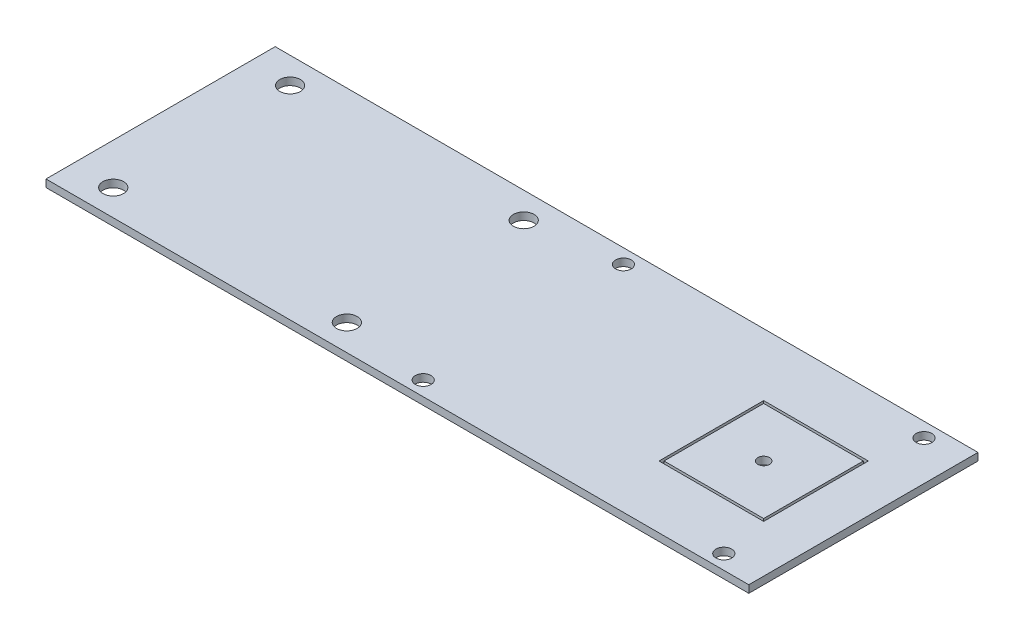
SolidWorks part; units mm, degrees
ref_plane "Front Plane" through (0, 0, 0) normal (0, 0, 1) x (1, 0, 0)
ref_plane "Top Plane" through (0, 0, 0) normal (0, 1, 0) x (1, 0, 0)
ref_plane "Right Plane" through (0, 0, 0) normal (1, 0, 0) x (0, 0, -1)
sketch "Sketch1" plane through (0, 0, 0) normal (0, 1, 0) x (1, 0, 0)
  line L0 (-62.28, 19.825) -> (-62.28, -19.825) construction
  line L1 (-70.525, -23) -> (70.525, -23)
  line L2 (-70.525, -23) -> (-70.525, 23)
  line L3 (-70.525, 23) -> (70.525, 23)
  line L4 (70.525, -23) -> (70.525, 23)
  line L5 (-70.525, -23) -> (70.525, 23) construction
  line L6 (-70.525, 23) -> (70.525, -23) construction
  line L7 (-64.355, -17.75) -> (-13.325, -17.75) construction
  line L8 (2.27, 18.515) -> (2.27, -18.515) construction
  line L9 (3.845, -20.09) -> (61.025, -20.09) construction
  line L10 (-62.28, 17.75) -> (-15.4, -17.75) construction
  circle A0 centre (-62.28, -17.75) radius 2.075
  circle A1 centre (-15.4, -17.75) radius 2.075
  circle A2 centre (-15.4, 17.75) radius 2.075
  circle A3 centre (-62.28, 17.75) radius 2.075
  circle A4 centre (2.27, -20.09) radius 1.575
  circle A5 centre (62.6, -20.09) radius 1.575
  circle A6 centre (62.6, 20.09) radius 1.575
  circle A7 centre (2.27, 20.09) radius 1.575
  circle A8 centre (50.51, 0) radius 1.185
  point P0 (0, 0)
  point P18 (-62.28, 0)
  point P31 (64.175, -20.09)
  point P32 (62.6, -21.665)
  point P33 (51.695, 0)
  point P34 (2.27, 0)
  point P37 (-38.84, 0)
  dimension "D6" = 4.15
  dimension "D12" = 3.15
  dimension "D16" = 2.37
  dimension "D1" = 141.05
  dimension "D2" = 46
  dimension "D5" = 39.65
  dimension "D7" = 6.17
  dimension "D8" = 51.03
  dimension "D11" = 37.03
  dimension "D13" = 57.18
  dimension "D14" = 6.35
  dimension "D15" = 18.83
  dimension "D3" = 2
  dimension "D4" = 2
  dimension "D9" = 2
  dimension "D10" = 2
extrude "Boss-Extrude1" add sketch "Sketch1" along normal blind 1.5
sketch "Sketch2" plane through (0, 1.5, 0) normal (0, 1, 0) x (1, 0, 0)
  line L1 (40.51, -10) -> (60.51, -10)
  line L2 (40.51, -10) -> (40.51, 10)
  line L3 (40.51, 10) -> (60.51, 10)
  line L4 (60.51, -10) -> (60.51, 10)
  line L5 (40.51, -10) -> (60.51, 10) construction
  line L6 (40.51, 10) -> (60.51, -10) construction
  point P0 (50.51, 0)
  dimension "D1" = 20
  dimension "D2" = 20
extrude "Cut-Extrude-Thin1" cut sketch "Sketch2" against normal blind 0.75 thin thin type one direction wall 0.5
ref_axis "Axis1" through (-38.84, 0, 0) along (0, 1, 0)
